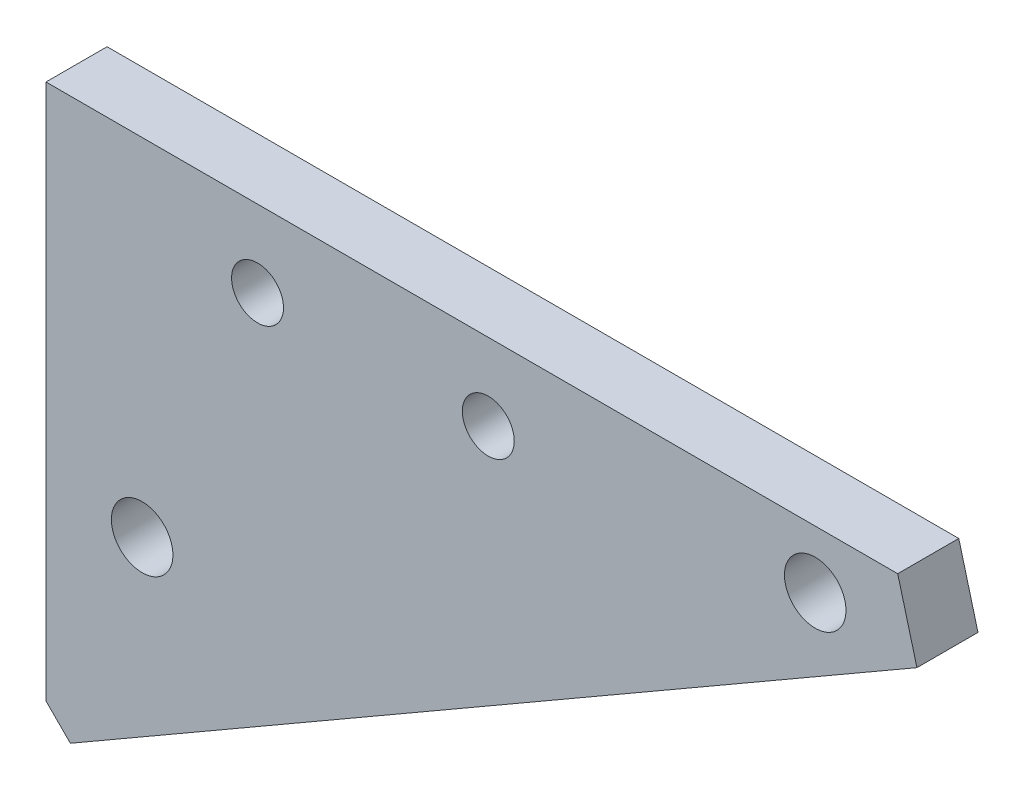
SolidWorks part; units mm, degrees
ref_plane "Front Plane" through (0, 0, 0) normal (0, 0, 1) x (1, 0, 0)
ref_plane "Top Plane" through (0, 0, 0) normal (0, 1, 0) x (1, 0, 0)
ref_plane "Right Plane" through (0, 0, 0) normal (1, 0, 0) x (0, 0, -1)
sketch "Sketch1" plane through (0, 0, 0) normal (0, 0, 1) x (1, 0, 0)
  line L0 (-6, 0) -> (6, 0)
  line L1 (-17, 10.289) -> (-17, -6.25)
  line L2 (-17, -6.25) -> (4.3359, -6.25)
  line L3 (-14.82, -6.25) -> (-14.82, -34)
  line L4 (-14.82, -24) -> (17.405, -24)
  point P4 (0, 0)
  dimension "D1" = 12
  dimension "D2" = 11
  dimension "D3" = 6.25
  dimension "D4" = 2.18
  dimension "D5" = 27.75
  dimension "D6" = 10
sketch "Sketch2" plane through (0, 0, 0) normal (0, 0, 1) x (1, 0, 0)
  line L0 (-12, -6.25) -> (17, -6.25) construction
  line L1 (-17, -6.25) -> (4.3359, -6.25) construction
  line L2 (17, -6.25) -> (17, 4) construction
  line L3 (17, 4) -> (-17, 4)
  line L4 (-17, 4) -> (-17, -25.8799)
  line L7 (-6, 0) -> (6, 0) construction
  line L8 (-17, 10.289) -> (-17, -6.25) construction
  line L9 (-17, -25.8799) -> (34.7535, 4)
  line L10 (34.7535, 4) -> (17, 4)
  dimension "D1" = 30
  dimension "D2" = 4
  dimension "D3" = 34
extrude "Boss-Extrude1" add sketch "Sketch2" along normal blind 3.175
hole_wizard "M2.5 Clearance Hole1" positions "Sketch3" profile "Sketch4" hole size "M2.5" standard "ANSI Metric" end condition through all
sketch "Sketch3" plane through (0, 0, 3.175) normal (0, 0, 1) x (1, 0, 0)
  point P0 (-6, 0)
  point P3 (6, 0)
sketch "Sketch4" plane through (-6, 0, 3.175) normal (1, 0, 0) x (0, -1, 0)
  line L0 (0, 0) -> (0, 3.175)
  line L1 (0, 3.175) -> (1.35, 3.175)
  line L2 (1.35, 3.175) -> (1.35, 0)
  line L5 (1.35, 0) -> (0, 0)
  line L11 (0, -6.35) -> (0, 107.95) construction
  dimension "Thru Hole Dia." = 2.7
  dimension "Thru Hole Depth" = 3.175
fillet "Fillet1" radius 2 1 edges at (34.7535, 4, 1.5875) profile chamfer
chamfer "Chamfer1" distance 2 angle 45 1 edges at (-17, -25.8799, 1.5875) first distance on face at (-17, -10.94, 1.5875)
hole_wizard "M3 Clearance Hole1" positions "Sketch5" profile "Sketch6" hole size "M3" standard "ANSI Metric" end condition through all
sketch "Sketch5" plane through (0, 0, 0) normal (0, 0, -1) x (-1, 0, 0)
  point P0 (-23, 1)
  point P2 (12, -14)
  dimension "D1" = 23
  dimension "D2" = 1
  dimension "D3" = 12
  dimension "D4" = 14
sketch "Sketch6" plane through (23, 1, 0) normal (1, 0, 0) x (0, 1, 0)
  line L0 (0, 0) -> (0, 3.175)
  line L1 (0, 3.175) -> (1.6, 3.175)
  line L2 (1.6, 3.175) -> (1.6, 0)
  line L5 (1.6, 0) -> (0, 0)
  line L11 (0, -6.35) -> (0, 107.95) construction
  dimension "Thru Hole Dia." = 3.2
  dimension "Thru Hole Depth" = 3.175
